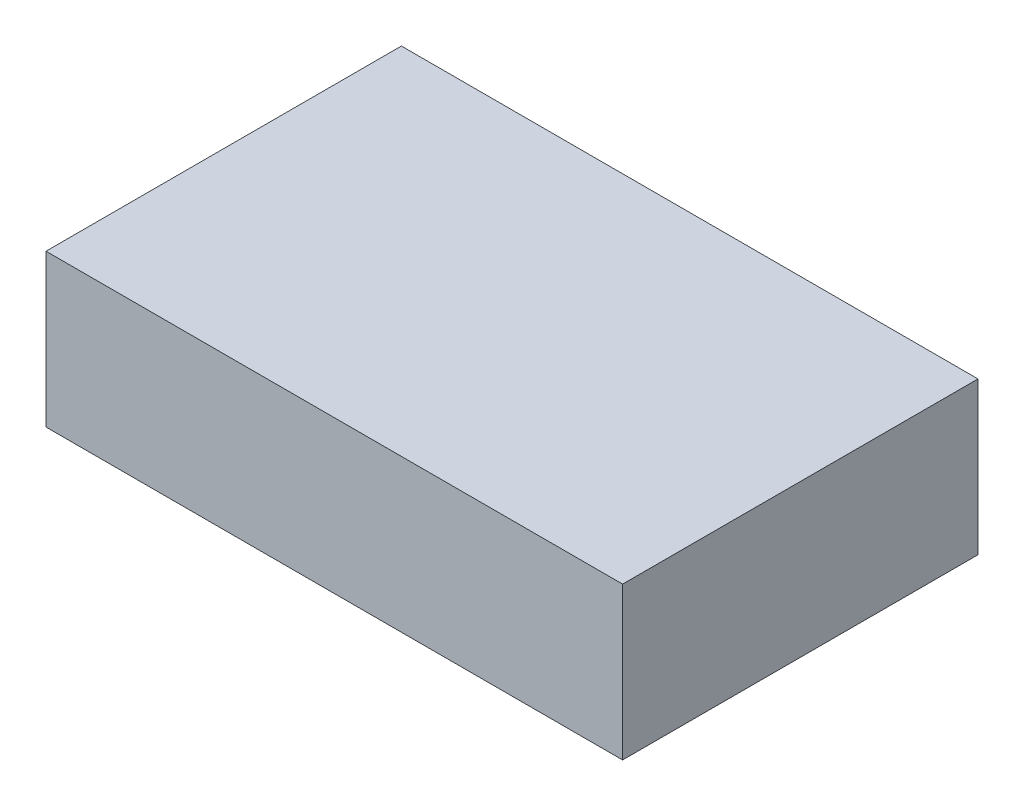
SolidWorks part; units mm, degrees
material "Malleable Cast Iron"
ref_plane "Front Plane" through (0, 0, 0) normal (0, 0, 1) x (1, 0, 0)
ref_plane "Top Plane" through (0, 0, 0) normal (0, 1, 0) x (1, 0, 0)
ref_plane "Right Plane" through (0, 0, 0) normal (1, 0, 0) x (0, 0, -1)
sketch "Sketch1" plane through (0, 0, 0) normal (0, 1, 0) x (1, 0, 0)
  line L1 (0, 0) -> (121.158, 0)
  line L2 (0, 0) -> (0, 74.676)
  line L3 (0, 74.676) -> (121.158, 74.676)
  line L4 (121.158, 0) -> (121.158, 74.676)
  dimension "D1" = 121.158
  dimension "D2" = 74.676
extrude "Boss-Extrude1" add sketch "Sketch1" along normal blind 32.004
